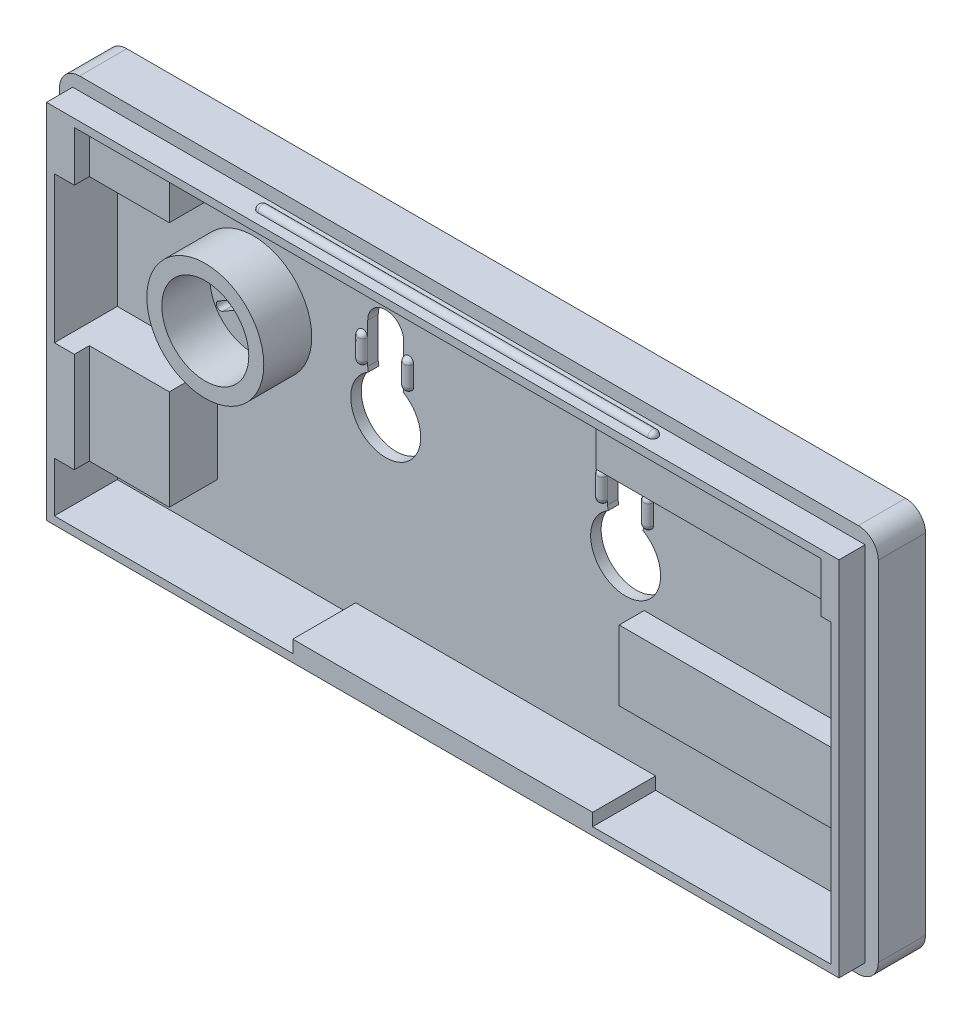
SolidWorks part; units mm, degrees
note: The reader was unsure of these and kept them because the rebuilt part matched: shared geometry of "Skizze1<3>", "Skizze1<4>", "Skizze1<5>", "Skizze1<6>", "Skizze1<7>".
ref_plane "Ebene vorne" through (0, 0, 0) normal (0, 0, 1) x (1, 0, 0)
ref_plane "Ebene oben" through (0, 0, 0) normal (0, 1, 0) x (1, 0, 0)
ref_plane "Ebene rechts" through (0, 0, 0) normal (1, 0, 0) x (0, 0, -1)
sketch "Skizze1" plane through (0, 0, 0) normal (0, 0, 1) x (1, 0, 0)
  line L1 (0, 0) -> (74, 0)
  line L2 (0, 0) -> (0, 33)
  line L3 (0, 33) -> (74, 33)
  line L4 (74, 0) -> (74, 33)
  line L5 (-2, 35) -> (76, 35)
  line L6 (-2, 35) -> (-2, -2)
  line L7 (-2, -2) -> (76, -2)
  line L8 (76, 35) -> (76, -2)
  line L9 (-0.75, 33.75) -> (74.75, 33.75)
  line L10 (-0.75, 33.75) -> (-0.75, -0.75)
  line L11 (-0.75, -0.75) -> (74.75, -0.75)
  line L12 (74.75, 33.75) -> (74.75, -0.75)
  circle A0 centre (11.75, 21.25) radius 4.35
  circle A1 centre (11.75, 21.25) radius 5.85
  dimension "D13" = 8.7
  dimension "D14" = 11.7
  dimension "D1" = 74
  dimension "D2" = 33
  dimension "D3" = 2
  dimension "D4" = 2
  dimension "D5" = 2
  dimension "D6" = 2
  dimension "D7" = 0.75
  dimension "D8" = 0.75
  dimension "D9" = 0.75
  dimension "D10" = 0.75
  dimension "D11" = 11.75
  dimension "D12" = 11.75
extrude "Aufsatz-Linear austragen1" add sketch "Skizze1" along normal blind 4.5 contours L5 L8 L7 L6
extrude "Aufsatz-Linear austragen2" add sketch "Skizze1<3>" along normal blind 7 contours L9 L12 L11 L10
sketch "Skizze1<3>" plane through (0, 0, 0) normal (0, 0, 1) x (1, 0, 0) same geometry as "Skizze1"
extrude "Schnitt-Linear austragen1" cut sketch "Skizze1<4>" along normal up to surface (7 mm away) contours L3 L4 L1 L2 up to face at (37, 16.5, 7)
sketch "Skizze1<4>" plane through (0, 0, 0) normal (0, 0, 1) x (1, 0, 0) same geometry as "Skizze1"
extrude "Aufsatz-Linear austragen3" add sketch "Skizze1<5>" along normal blind 1 contours L1 L4 L3 L2
sketch "Skizze1<5>" plane through (0, 0, 0) normal (0, 0, 1) x (1, 0, 0) same geometry as "Skizze1"
extrude "Aufsatz-Linear austragen4" add sketch "Skizze1<6>" along normal blind 1 contours A1 A0 | A0
sketch "Skizze1<6>" plane through (0, 0, 0) normal (0, 0, 1) x (1, 0, 0) same geometry as "Skizze1"
sketch "Skizze3" plane through (-2, 0, 0) normal (-1, 0, 0) x (0, 0, 1)
  line L0 (4.5, -0.75) -> (4.5, 33.75) construction
  line L1 (0, 35) -> (4.5, 35)
  line L2 (0, 35) -> (0, 27)
  line L3 (0, 27) -> (4.5, 27)
  line L4 (4.5, 35) -> (4.5, 27)
  dimension "D1" = 8
ref_plane "Ebene2" through (37, 0, 0) normal (1, 0, 0) x (0, 0, -1)
ref_plane "Ebene3" through (0, 16.5, 0) normal (0, -1, 0) x (-1, 0, 0)
scale "Skalieren1" scale about centroid uniform scaling yes scale factor 1.05
sketch "Skizze4" plane through (0, 0, -0.0831) normal (0, 0, -1) x (-1, 0, 0)
  line L1 (-3.465, 16.5) -> (3.465, 16.5) construction
  line L2 (-49, 21.5) -> (-49, 25.5) construction
  line L5 (-50.8, 21.5) -> (-50.8, 25.5)
  line L6 (-47.2, 21.5) -> (-47.2, 25.5)
  line L7 (-37, 3.465) -> (-37, -3.465) construction
  circle A0 centre (-49, 18) radius 3.5
  arc A3 (-50.8, 21.5) -> (-47.2, 21.5) centre (-49, 21.5) ccw
  arc A4 (-47.2, 25.5) -> (-50.8, 25.5) centre (-49, 25.5) ccw
  point P8 (-49, 23.5)
  dimension "D2" = 7
  dimension "D4" = 1.8
  dimension "D1" = 12
  dimension "D3" = 4
  dimension "D5" = 7
extrude "Schnitt-Linear austragen2" cut sketch "Skizze4" against normal up to surface (1.05 mm away) contours L6 A4 L5 A3 | A0
mirror "Spiegeln1" about plane through (37, 0, 0) normal (1, 0, 0) of "Schnitt-Linear austragen2"
sketch "Skizze5" plane through (-1.85, 0, 0) normal (1, 0, 0) x (0, 0, -1)
  line L0 (-0.9669, -0.825) -> (-0.9669, 33.825) construction
  line L1 (-0.9669, 14.175) -> (-7.2669, 14.175)
  line L2 (-0.9669, 14.175) -> (-0.9669, 4.175)
  line L3 (-0.9669, 4.175) -> (-7.2669, 4.175)
  line L4 (-7.2669, 14.175) -> (-7.2669, 4.175)
  line L5 (-7.2669, -0.825) -> (-7.2669, 33.825) construction
  line L7 (-7.2669, -0.825) -> (-0.9669, -0.825) construction
  line L8 (-0.9669, 33.825) -> (-7.2669, 33.825)
  line L13 (-0.9669, 33.825) -> (-0.9669, 28.825)
  line L14 (-0.9669, 28.825) -> (-7.2669, 28.825)
  line L15 (-7.2669, 33.825) -> (-7.2669, 28.825)
  dimension "D1" = 15
  dimension "D2" = 10
  dimension "D3" = 5
extrude "Aufsatz-Linear austragen5" add sketch "Skizze5" along normal blind 10
sketch "Skizze6" plane through (75.85, 0, 0) normal (-1, 0, 0) x (0, 0, 1)
  line L0 (0.9669, -0.825) -> (0.9669, 33.825) construction
  line L1 (0.9669, 14.175) -> (3.4669, 14.175)
  line L2 (0.9669, 14.175) -> (0.9669, 7.175)
  line L3 (0.9669, 7.175) -> (3.4669, 7.175)
  line L4 (3.4669, 14.175) -> (3.4669, 7.175)
  line L5 (7.2669, -0.825) -> (0.9669, -0.825) construction
  line L6 (7.2669, -0.825) -> (7.2669, 33.825) construction
  line L7 (0.9669, 33.825) -> (7.2669, 33.825)
  line L8 (0.9669, 33.825) -> (0.9669, 28.825)
  line L9 (0.9669, 28.825) -> (7.2669, 28.825)
  line L10 (7.2669, 33.825) -> (7.2669, 28.825)
  dimension "D1" = 2.5
  dimension "D2" = 7
  dimension "D3" = 15
  dimension "D4" = 5
extrude "Aufsatz-Linear austragen6" add sketch "Skizze6" along normal blind 25
sketch "Skizze10" plane through (0, 0, 7.2669) normal (0, 0, 1) x (1, 0, 0)
  line L0 (8.15, 33.825) -> (50.85, 33.825) construction
  line L1 (8.15, 28.825) -> (0.15, 28.825)
  line L2 (8.15, 28.825) -> (8.15, 33.825)
  line L3 (8.15, 33.825) -> (0.15, 33.825)
  line L4 (0.15, 28.825) -> (0.15, 33.825)
  line L5 (-1.85, 14.175) -> (-1.85, 28.825) construction
  line L6 (8.15, 4.175) -> (-1.85, 4.175) construction
  line L7 (8.15, 14.175) -> (0.15, 14.175)
  line L8 (8.15, 14.175) -> (8.15, 4.175)
  line L9 (8.15, 4.175) -> (0.15, 4.175)
  line L10 (0.15, 14.175) -> (0.15, 4.175)
  line L11 (-1.85, -0.825) -> (-1.85, 4.175) construction
  line L12 (75.85, -0.825) -> (75.85, 28.825) construction
  line L13 (50.85, 28.825) -> (74.85, 28.825)
  line L14 (50.85, 28.825) -> (50.85, 33.825)
  line L15 (50.85, 33.825) -> (74.85, 33.825)
  line L16 (74.85, 28.825) -> (74.85, 33.825)
  dimension "D1" = 0
  dimension "D2" = 2
  dimension "D3" = 2
  dimension "D4" = 1
  dimension "D5" = 0
extrude "Schnitt-Linear austragen4" cut sketch "Skizze10" against normal blind 1.5
sketch "Skizze7" plane through (0, 34.6125, 0) normal (0, 1, 0) x (1, 0, 0)
  line L0 (12, -5.7669) -> (62, -5.7669) construction
  line L1 (12, -5.2669) -> (62, -5.2669)
  line L2 (12, -6.2669) -> (62, -6.2669)
  line L3 (37, -3.465) -> (37, 3.465) construction
  line L5 (-2.6375, -7.2669) -> (76.6375, -7.2669) construction
  arc A0 (12, -5.2669) -> (12, -6.2669) centre (12, -5.7669) ccw
  arc A1 (62, -6.2669) -> (62, -5.2669) centre (62, -5.7669) ccw
  point P2 (37, -5.7669)
  dimension "D2" = 0.5
  dimension "D1" = 50
  dimension "D3" = 25
  dimension "D4" = 1.5
extrude "Aufsatz-Linear austragen8" add sketch "Skizze1<7>" along normal up to surface (5.7669 mm away) contours A1 A0 up to face at (4.15, 31.325, 5.7669)
sketch "Skizze1<7>" plane through (0, 0, 0) normal (0, 0, 1) x (1, 0, 0) same geometry as "Skizze1"
sketch "Skizze8" plane through (0, 0, 0.9669) normal (0, 0, 1) x (1, 0, 0)
  line L0 (8.4591, 23.1499) -> (10.6241, 21.8999) construction
  line L1 (8.6591, 23.4963) -> (10.8241, 22.2463)
  line L2 (8.2591, 22.8035) -> (10.4241, 21.5535)
  line L3 (7.4, 21.25) -> (16.1, 21.25)
  line L4 (11.7499, 25.05) -> (11.7499, 22.55) construction
  line L5 (12.1499, 25.05) -> (12.1499, 22.55)
  line L6 (11.3499, 25.05) -> (11.3499, 22.55)
  line L7 (15.0408, 23.1501) -> (12.8758, 21.9001) construction
  line L8 (15.2408, 22.8037) -> (13.0758, 21.5537)
  line L9 (14.8408, 23.4965) -> (12.6758, 22.2465)
  line L10 (15.0409, 19.3501) -> (12.8759, 20.6001) construction
  line L11 (14.8409, 19.0037) -> (12.6759, 20.2537)
  line L12 (15.2409, 19.6965) -> (13.0759, 20.9465)
  line L13 (11.7501, 17.45) -> (11.7501, 19.95) construction
  line L14 (11.3501, 17.45) -> (11.3501, 19.95)
  line L15 (12.1501, 17.45) -> (12.1501, 19.95)
  line L16 (8.4592, 19.3499) -> (10.6242, 20.5999) construction
  line L17 (8.2592, 19.6963) -> (10.4242, 20.9463)
  line L18 (8.6592, 19.0035) -> (10.8242, 20.2535)
  arc A0 (8.6591, 23.4963) -> (8.2591, 22.8035) centre (8.4591, 23.1499) ccw
  arc A1 (10.4241, 21.5535) -> (10.8241, 22.2463) centre (10.6241, 21.8999) ccw
  circle A2 centre (11.75, 21.25) radius 4.35 construction
  arc A3 (12.1499, 25.05) -> (11.3499, 25.05) centre (11.7499, 25.05) ccw
  arc A4 (11.3499, 22.55) -> (12.1499, 22.55) centre (11.7499, 22.55) ccw
  arc A5 (15.2408, 22.8037) -> (14.8408, 23.4965) centre (15.0408, 23.1501) ccw
  arc A6 (12.6758, 22.2465) -> (13.0758, 21.5537) centre (12.8758, 21.9001) ccw
  arc A7 (14.8409, 19.0037) -> (15.2409, 19.6965) centre (15.0409, 19.3501) ccw
  arc A8 (13.0759, 20.9465) -> (12.6759, 20.2537) centre (12.8759, 20.6001) ccw
  arc A9 (11.3501, 17.45) -> (12.1501, 17.45) centre (11.7501, 17.45) ccw
  arc A10 (12.1501, 19.95) -> (11.3501, 19.95) centre (11.7501, 19.95) ccw
  arc A11 (8.2592, 19.6963) -> (8.6592, 19.0035) centre (8.4592, 19.3499) ccw
  arc A12 (10.8242, 20.2535) -> (10.4242, 20.9463) centre (10.6242, 20.5999) ccw
  point P2 (9.5416, 22.5249)
  point P16 (11.7499, 23.8)
  point P23 (13.9583, 22.5251)
  point P30 (13.9584, 19.9751)
  point P37 (11.7501, 18.7)
  point P44 (9.5417, 19.9749)
  point P49 (11.75, 21.25)
  dimension "D2" = 0.4
  dimension "D1" = 2.5
  dimension "D3" = 2.55
  dimension "D4" = 0.0001
  dimension "D5" = 8.7
  dimension "D6" = 30
  dimension "D7" = 6
extrude "Schnitt-Linear austragen3" cut sketch "Skizze8" along a picked direction on the side against the normal up to surface (1.05 mm away) contours L6 A4 L5 A3 | L2 A1 L1 A0 | L9 A6 L8 A5 | L12 A8 L11 A7 | L15 A10 L14 A9 | L18 A12 L17 A11
sketch "Skizze9" plane through (0, -1.6125, 0) normal (0, -1, 0) x (1, 0, 0)
  line L0 (17, 5.7669) -> (37, 5.7669)
  line L1 (37, 5.7669) -> (37, 5.2669)
  line L2 (37, 5.2669) -> (17.5, 5.2669)
  line L3 (37, -3.465) -> (37, 3.465) construction
  line L4 (-2.6375, 7.2669) -> (76.6375, 7.2669) construction
  arc A0 (17, 5.7669) -> (17.5, 5.2669) centre (17.5, 5.7669) ccw
  dimension "D5" = 2
  dimension "D1" = 0.5
  dimension "D2" = 0
  dimension "D3" = 0.5
  dimension "D4" = 20
revolve "Rotation1" add sketch "Skizze9" angle 180 about L0
mirror "Spiegeln2" about plane through (-2.6375, -1.6125, 7.2669) normal (0, 1, 0) of "Rotation1"
mirror "Spiegeln3" about plane through (37, 0, 0) normal (1, 0, 0) of "Spiegeln2"
mirror "Spiegeln4" about plane through (0, 16.5, 0) normal (0, -1, 0) of "Spiegeln2", "Spiegeln3"
fillet "Verrundung1" radius 2 4 edges at (-3.95, 35.925, 2.2794) (-3.95, -2.925, 2.2794) (77.95, -2.925, 2.2794) (77.95, 35.925, 2.2794)
sketch "Skizze12" plane through (0, 0, 0.9669) normal (0, 0, 1) x (1, 0, 0)
  line L0 (22.7, 24.5) -> (22.7, 21.5)
  line L1 (23.2, 24) -> (23.2, 22)
  line L2 (23.2, 21.5) -> (23.2, 25.5) construction
  arc A0 (22.7, 21.5) -> (23.2, 22) centre (22.7, 22) ccw
  arc A1 (22.7, 24.5) -> (23.2, 24) centre (22.7, 24) cw
  point P8 (23.2, 21.1811)
  point P9 (22.7, 21.7951)
  point P10 (23.2, 22.1582)
  dimension "D2" = 0.5
  dimension "D3" = 0.5
  dimension "D5" = 0.5
  dimension "D1" = 360
  dimension "D4" = 3
  dimension "D6" = 0.5
revolve "Rotation2" add sketch "Skizze12" angle 360 about L0
ref_plane "Ebene4" through (25, 0, 0) normal (1, 0, 0) x (0, 0, -1)
mirror "Spiegeln5" about plane through (25, 0, 0) normal (1, 0, 0) of "Rotation2"
mirror "Spiegeln6" about plane through (37, 0, 0) normal (1, 0, 0) of "Spiegeln5", "Rotation2"
sketch "Skizze13" plane through (0, 0, 0.9669) normal (0, 0, 1) x (1, 0, 0)
  line L0 (-1.85, -0.825) -> (75.85, -0.825) construction
  line L1 (22, -0.825) -> (52, -0.825)
  line L2 (22, -0.825) -> (22, 0.425)
  line L3 (22, 0.425) -> (52, 0.425)
  line L4 (52, -0.825) -> (52, 0.425)
  line L5 (37, -3.465) -> (37, 3.465) construction
  line L6 (8.15, 33.825) -> (50.85, 33.825) construction
  dimension "D1" = 30
  dimension "D2" = 15
  dimension "D3" = 33.4
extrude "Aufsatz-Linear austragen9" add sketch "Skizze13" along normal up to surface (6.3 mm away) up to face at (17.6, 21.25, 0.9669)
equation "\"D4@Skizze1\"=\"D3@Skizze1\""
equation "\"D5@Skizze1\"=\"D3@Skizze1\""
equation "\"D6@Skizze1\"=\"D3@Skizze1\""
equation "\"D8@Skizze1\"=\"D7@Skizze1\""
equation "\"D9@Skizze1\"=\"D7@Skizze1\""
equation "\"D10@Skizze1\"=\"D7@Skizze1\""
equation "\"D12@Skizze1\"=\"D11@Skizze1\""
equation "\"D3@Skizze7\"=\"D1@Skizze7\"/2"
equation "\"D3@Skizze9\"=\"D1@Skizze9\""
equation "\"D5@Skizze12\"=\"D3@Skizze12\""
equation "\"D2@Skizze13\"=\"D1@Skizze13\"/2"
